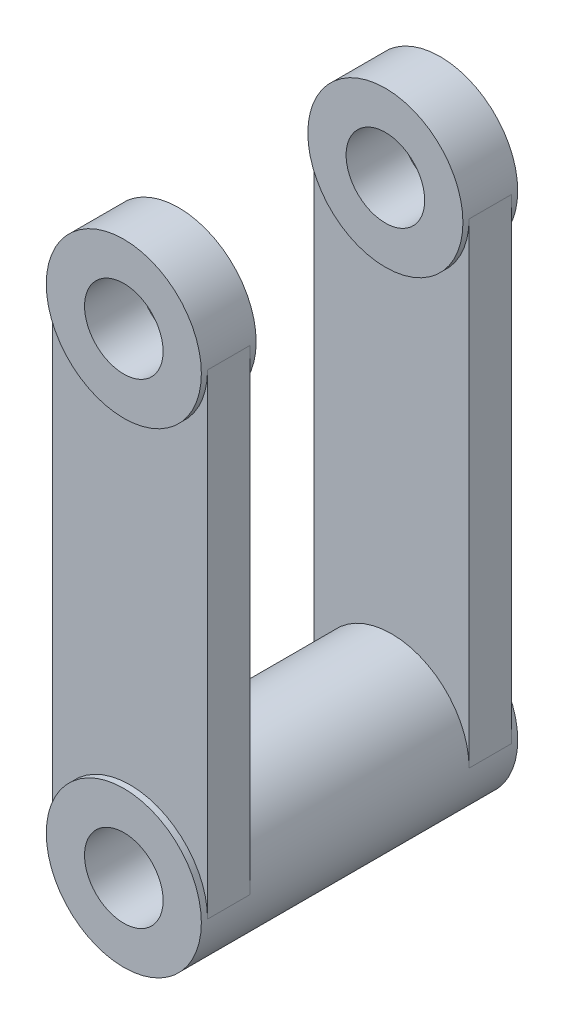
SolidWorks part; units mm, degrees
ref_plane "Front Plane" through (0, 0, 0) normal (0, 0, 1) x (1, 0, 0)
ref_plane "Top Plane" through (0, 0, 0) normal (0, 1, 0) x (1, 0, 0)
ref_plane "Right Plane" through (0, 0, 0) normal (1, 0, 0) x (0, 0, -1)
sketch "Sketch1" plane through (0, 0, 0) normal (0, 0, 1) x (1, 0, 0)
  circle A0 centre (0, 0) radius 38
  circle A1 centre (0, 0) radius 75
  dimension "D1" = 150
  dimension "D2" = 76
extrude "Boss-Extrude1" add sketch "Sketch1" along normal mid plane 306
sketch "Sketch4" plane through (0, 0, 153) normal (0, 0, 1) x (1, 0, 0)
  line L0 (-75, 0) -> (-75, 460)
  line L1 (75, 0) -> (75, 460)
  circle A0 centre (0, 0) radius 75 construction
  circle A1 centre (0, 460) radius 75
  circle A2 centre (0, 460) radius 38
  point P9 (0, 0)
  point P10 (-75, 400.5409)
  point P12 (-75, 460)
  circle M3 centre (0, 0) radius 75
  dimension "D1" = 76
  dimension "D2" = 150
  dimension "D3" = 460
extrude "Boss-Extrude2" add sketch "Sketch4" against normal blind 41 from offset 6 contours A1 L0 L1 M3 region at (0, 230, 153) offset against normal yes
extrude "Boss-Extrude3" add sketch "Sketch4<6>" against normal blind 53 contours A1 A2 region at (0, 387.1213, 153)
sketch "Sketch4<6>" plane through (0, 0, 153) normal (0, 0, 1) x (1, 0, 0) same geometry as "Sketch4"
mirror "Mirror1" about plane through (0, 0, 0) normal (0, 0, 1) of "Boss-Extrude3", "Boss-Extrude2"
